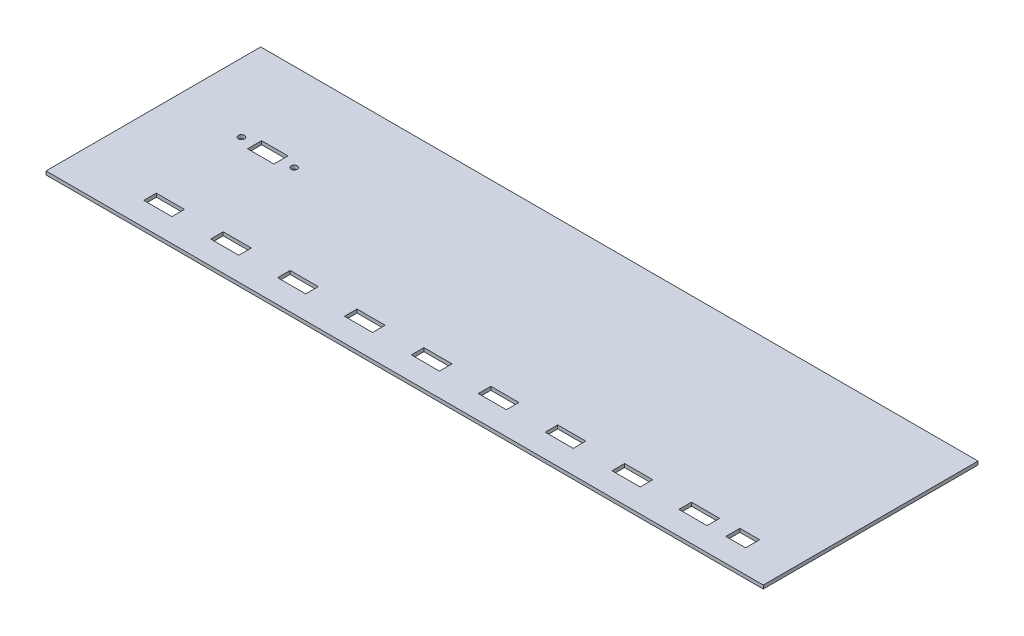
SolidWorks part; units mm, degrees
ref_plane "Front Plane" through (0, 0, 0) normal (0, 0, 1) x (1, 0, 0)
ref_plane "Top Plane" through (0, 0, 0) normal (0, 1, 0) x (1, 0, 0)
ref_plane "Right Plane" through (0, 0, 0) normal (1, 0, 0) x (0, 0, -1)
sketch "Sketch1" plane through (0, 0, 0) normal (0, 1, 0) x (1, 0, 0)
  line L0 (309.09, 20.45) -> (325.09, 20.45)
  line L1 (0, 0) -> (408.5, 0)
  line L2 (0, 0) -> (0, 122.3)
  line L3 (0, 122.3) -> (408.5, 122.3)
  line L4 (408.5, 0) -> (408.5, 122.3)
  line L5 (373.875, 21.3) -> (385.125, 21.3)
  line L6 (373.875, 21.3) -> (373.875, 13.3)
  line L7 (373.875, 13.3) -> (385.125, 13.3)
  line L8 (385.125, 21.3) -> (385.125, 13.3)
  line L9 (347.19, 20.45) -> (363.19, 20.45)
  line L10 (347.19, 20.45) -> (347.19, 13.3)
  line L11 (347.19, 13.3) -> (363.19, 13.3)
  line L12 (363.19, 20.45) -> (363.19, 13.3)
  line L13 (309.09, 20.45) -> (309.09, 13.3)
  line L14 (325.09, 20.45) -> (325.09, 13.3)
  line L15 (309.09, 13.3) -> (325.09, 13.3)
  line L16 (270.99, 20.45) -> (286.99, 20.45)
  line L17 (270.99, 20.45) -> (270.99, 13.3)
  line L18 (286.99, 20.45) -> (286.99, 13.3)
  line L19 (270.99, 13.3) -> (286.99, 13.3)
  line L20 (232.89, 20.45) -> (248.89, 20.45)
  line L21 (232.89, 20.45) -> (232.89, 13.3)
  line L22 (248.89, 20.45) -> (248.89, 13.3)
  line L23 (232.89, 13.3) -> (248.89, 13.3)
  line L24 (194.79, 20.45) -> (210.79, 20.45)
  line L25 (194.79, 20.45) -> (194.79, 13.3)
  line L26 (210.79, 20.45) -> (210.79, 13.3)
  line L27 (194.79, 13.3) -> (210.79, 13.3)
  line L28 (156.69, 20.45) -> (172.69, 20.45)
  line L29 (156.69, 20.45) -> (156.69, 13.3)
  line L30 (172.69, 20.45) -> (172.69, 13.3)
  line L31 (156.69, 13.3) -> (172.69, 13.3)
  line L32 (118.59, 20.45) -> (134.59, 20.45)
  line L33 (118.59, 20.45) -> (118.59, 13.3)
  line L34 (134.59, 20.45) -> (134.59, 13.3)
  line L35 (118.59, 13.3) -> (134.59, 13.3)
  line L36 (80.49, 20.45) -> (96.49, 20.45)
  line L37 (80.49, 20.45) -> (80.49, 13.3)
  line L38 (96.49, 20.45) -> (96.49, 13.3)
  line L39 (80.49, 13.3) -> (96.49, 13.3)
  line L40 (42.39, 20.45) -> (58.39, 20.45)
  line L41 (42.39, 20.45) -> (42.39, 13.3)
  line L42 (58.39, 20.45) -> (58.39, 13.3)
  line L43 (42.39, 13.3) -> (58.39, 13.3)
  line L45 (46.5, 76.3) -> (61.5, 76.3)
  line L46 (46.5, 76.3) -> (46.5, 68.3)
  line L47 (46.5, 68.3) -> (61.5, 68.3)
  line L48 (61.5, 76.3) -> (61.5, 68.3)
  circle A0 centre (39, 72.3) radius 1.75
  circle A1 centre (69, 72.3) radius 1.75
  point P53 (0, 0)
  point P54 (61.5, 72.3)
  point P55 (59.9114, 80.3441)
  point P56 (0, 0)
  point P58 (71.351, 79.4361)
  dimension "D12" = 3.5
  dimension "D1" = 408.5
  dimension "D2" = 122.3
  dimension "D3" = 11.25
  dimension "D4" = 34.625
  dimension "D5" = 8
  dimension "D6" = 13.3
  dimension "D7" = 16
  dimension "D8" = 7.15
  dimension "D9" = 45.31
  dimension "D11" = 38.1
  dimension "D13" = 30
  dimension "D14" = 15
  dimension "D15" = 7.5
  dimension "D16" = 8
  dimension "D17" = 39
  dimension "D18" = 50
  dimension "D10" = 9
extrude "Boss-Extrude1" add sketch "Sketch1" along normal blind 2
equation "\"D15@Sketch1\"=(\"D13@Sketch1\"-\"D14@Sketch1\")/2"
